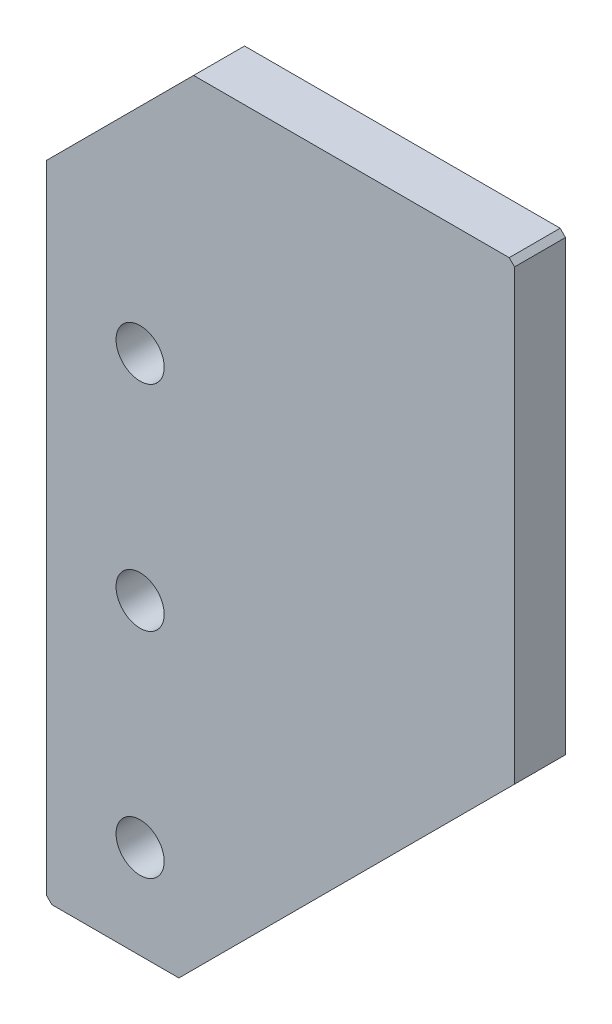
SolidWorks part; units mm, degrees
material "6061-T6 (SS)"
ref_plane "Front Plane" through (0, 0, 0) normal (0, 0, 1) x (1, 0, 0)
ref_plane "Top Plane" through (0, 0, 0) normal (0, 1, 0) x (1, 0, 0)
ref_plane "Right Plane" through (0, 0, 0) normal (1, 0, 0) x (0, 0, -1)
sketch "Sketch1" plane through (0, 0, 0) normal (0, 0, 1) x (1, 0, 0)
  line L0 (-25, 19.9957) -> (-25, -0.608) construction
  line L1 (-35, -0.608) -> (-35, 13.6457) construction
  line L2 (-55, 60) -> (-55, 20) construction
  line L3 (-55, 20) -> (-55, -20) construction
  line L4 (5.2388, 0) -> (-5.2388, 0) construction
  line L5 (-72.5, -37.5) -> (-47.7513, -37.5)
  line L6 (-47.7513, -37.5) -> (15, 25.2513)
  line L7 (15, 25.2513) -> (15, 110)
  line L8 (15, 110) -> (-45, 110)
  line L9 (-72.5, 82.5) -> (-72.5, -37.5)
  line L10 (-45, 110) -> (-72.5, 82.5)
  point P8 (-55, 0)
  point P13 (-72.5, 110)
  dimension "D1" = 10
  dimension "D2" = 25
  dimension "D3" = 40
  dimension "D4" = 20
  dimension "D5" = 17.5
  dimension "D6" = 17.5
  dimension "D7" = 17.5
  dimension "D8" = 110
  dimension "D9" = 10
  dimension "D10" = 45
  dimension "D11" = 50
extrude "Boss-Extrude1" add sketch "Sketch1" along normal mid plane 9.525
hole_wizard "M8 Clearance Hole1" positions "Sketch2" profile "Sketch3" hole size "M8" standard "ANSI Metric" end condition up to next
sketch "Sketch2" plane through (0, 0, 4.7625) normal (0, 0, 1) x (1, 0, 0)
  point P0 (-55, 60)
  point P3 (-55, 20)
  point P6 (-55, -20)
sketch "Sketch3" plane through (-55, 60, 4.7625) normal (1, 0, 0) x (0, -1, 0)
  line L0 (0, 0) -> (0, 9.525)
  line L1 (0, 9.525) -> (4.5, 9.525)
  line L2 (4.5, 9.525) -> (4.5, 0)
  line L5 (4.5, 0) -> (0, 0)
  line L11 (0, -6.35) -> (0, 107.95) construction
  dimension "Thru Hole Dia." = 9
  dimension "Thru Hole Depth" = 9.525
chamfer "Chamfer1" distance 1 2 edges at (15, 110, 0) (-72.5, -37.5, 0)
